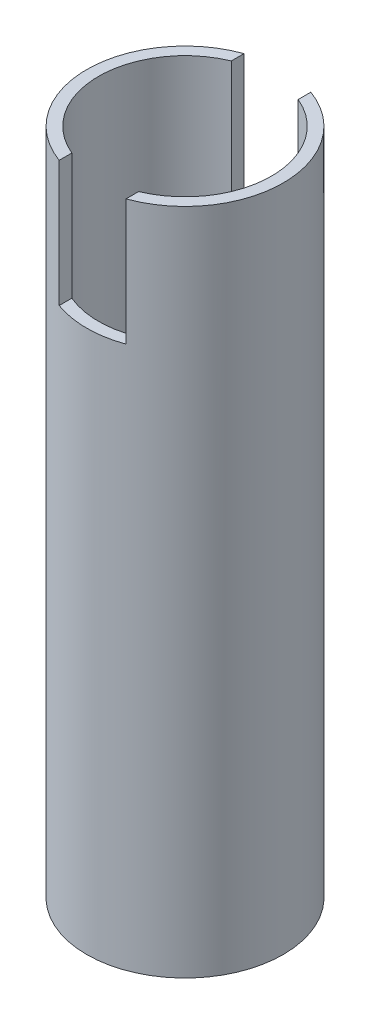
SolidWorks part; units mm, degrees
material "PVC 0.007 Plasticizado"
ref_plane "Plano frontal" through (0, 0, 0) normal (0, 0, 1) x (1, 0, 0)
ref_plane "Plano superior" through (0, 0, 0) normal (0, 1, 0) x (1, 0, 0)
ref_plane "Plano direito" through (0, 0, 0) normal (1, 0, 0) x (0, 0, -1)
sketch "Esboço1" plane through (0, 0, 0) normal (0, 1, 0) x (1, 0, 0)
  circle A0 centre (0, 0) radius 25
  circle A1 centre (0, 0) radius 22
  dimension "D1" = 44
  dimension "D2" = 3
extrude "Ressalto-extrusão1" add sketch "Esboço1" along normal blind 170
sketch "Esboço3" plane through (0, 170, 0) normal (0, 1, 0) x (1, 0, 0)
  line L0 (12.7319, 0) -> (-47.995, 0) construction
  line L1 (0, -27.2162) -> (0, 16.6302) construction
  line L2 (8.5, -20.2916) -> (8.5, -23.5106)
  line L3 (-8.5, -20.2916) -> (-8.5, -23.5106)
  line L4 (-8.5, 23.5106) -> (-8.5, 20.2916)
  line L5 (8.5, 20.2916) -> (8.5, 23.5106)
  arc A0 (8.5, -20.2916) -> (-8.5, -20.2916) centre (0, 0) cw
  circle A1 centre (0, 0) radius 22 construction
  arc A2 (8.5, -23.5106) -> (-8.5, -23.5106) centre (0, 0) cw
  circle A3 centre (0, 0) radius 25 construction
  arc A4 (-8.5, 20.2916) -> (8.5, 20.2916) centre (0, 0) cw
  arc A5 (8.5, 23.5106) -> (-8.5, 23.5106) centre (0, 0) ccw
  dimension "D1" = 17
extrude "Corte-extrusão2" cut sketch "Esboço3" against normal blind 32
